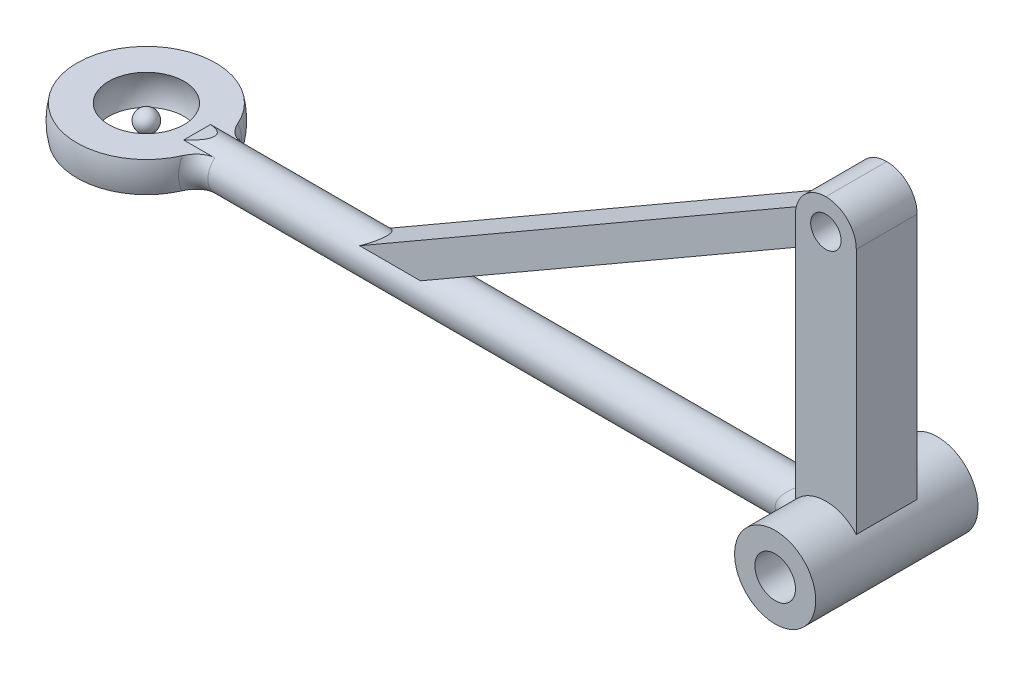
SolidWorks part; units mm, degrees
ref_plane "前视基准面" through (0, 0, 0) normal (0, 0, 1) x (1, 0, 0)
ref_plane "上视基准面" through (0, 0, 0) normal (0, 1, 0) x (1, 0, 0)
ref_plane "右视基准面" through (0, 0, 0) normal (1, 0, 0) x (0, 0, -1)
other "Configuration Table"
sketch "草图1" plane through (0, 0, 0) normal (0, 0, 1) x (1, 0, 0)
  line L0 (0, 0.75) -> (0, -0.75) construction
  line L1 (5, -0.75) -> (-5, -0.75)
  line L2 (5, -0.75) -> (5, 0.75)
  line L3 (5, 0.75) -> (-5, 0.75)
  line L4 (-5, -0.75) -> (-5, 0.75)
  line L5 (5, -0.75) -> (-5, 0.75) construction
  line L6 (5, 0.75) -> (-5, -0.75) construction
  circle A0 centre (0, 0) radius 3.5
  circle A1 centre (0, 0) radius 2
  dimension "D1" = 4
  dimension "D2" = 1.5
  dimension "D3" = 1.5
  dimension "D4" = 10
revolve "旋转1" add sketch "草图1" angle 360 about L0 region at (-2.7121, 0, 0)
sketch "草图2" plane through (0, 0, 0) normal (0, 0, 1) x (1, 0, 0)
  line L0 (0, 0) -> (35, 0) construction
  circle A0 centre (35, 0) radius 1
  circle A1 centre (35, 0) radius 2
  dimension "D2" = 2
  dimension "D3" = 1
  dimension "D1" = 35
extrude "凸台-拉伸1" add sketch "草图2" along normal mid plane 8 separate body
sketch "草图3" plane through (0, 0, 0) normal (0, 1, 0) x (1, 0, 0)
  line L0 (-0.5, 0) -> (0.5, 0)
  line L1 (37, 4) -> (33, 4) construction
  line L2 (35, 4) -> (35, 0) construction
  line L3 (35, 0) -> (0, 0) construction
  line L4 (2.5, 0) -> (33.9, 0)
  line L5 (2.5, 0) -> (2.5, 1)
  line L6 (2.5, 1) -> (33.9, 1)
  line L7 (33.9, 0) -> (33.9, 1)
  arc A0 (0.5, 0) -> (-0.5, 0) centre (0, 0) ccw
  dimension "D4" = 1
  dimension "D1" = 1
  dimension "D2" = 2.5
  dimension "D3" = 1.1
revolve "旋转2" add sketch "草图3" angle 360 about L4
sketch "草图4" plane through (0, 0, 0) normal (0, 0, 1) x (1, 0, 0)
  line L0 (2.5, 0.75) -> (2.5, 1)
  line L1 (2.5, 1) -> (3.3541, 1)
  line L2 (3.3541, 1) -> (2.5, 0.75)
  line L3 (3.3541, -0.75) -> (3.3541, 0.75) construction
  line L4 (0, 0) -> (3.8322, 0) construction
  line L5 (3.3541, -1) -> (2.5, -0.75)
  line L6 (2.5, -1) -> (3.3541, -1)
  line L7 (2.5, -0.75) -> (2.5, -1)
extrude "切除-拉伸1" cut sketch "草图4" against normal mid plane 10
fillet "圆角1" radius 1 3 edges at (33.0025, 0.1009, -0.9949) (3.3541, 0, -1) (3.3541, 0, 1)
sketch "草图5" plane through (0, 0, 0) normal (0, 0, 1) x (1, 0, 0)
  line L0 (35, 1.3229) -> (35, 0) construction
  line L1 (36.5, 1.3229) -> (33.5, 1.3229)
  line L2 (36.5, 1.3229) -> (36.5, 15)
  line L3 (36.5, 15) -> (33.5, 15)
  line L4 (33.5, 1.3229) -> (33.5, 15)
  line L5 (35, 15) -> (35, 13.5) construction
  circle A0 centre (35, 0) radius 2 construction
  circle A1 centre (35, 13.5) radius 0.75
  dimension "D3" = 1.5
  dimension "D4" = 1.5
  dimension "D1" = 3
  dimension "D2" = 15
extrude "凸台-拉伸2" add sketch "草图5" along normal mid plane 3
fillet "圆角2" radius 1.5 2 edges at (33.5, 15, 0) (36.5, 15, 0)
sketch "草图6" plane through (0, 0, 0) normal (0, 0, 1) x (1, 0, 0)
  line L0 (33.5, 13.5) -> (10.1173, 0)
  line L1 (33.5, 13.5) -> (33.5, 1.3229) construction
  line L2 (10.1173, 0) -> (13.1173, 0)
  line L3 (13.1173, 0) -> (33.5, 11.7679)
  line L4 (33.5, 11.7679) -> (33.5, 13.5)
  line L5 (13.1173, 0) -> (35, 0) construction
  arc A0 (35, 15) -> (33.5, 13.5) centre (35, 13.5) ccw construction
  dimension "D1" = 1.5
  dimension "D2" = 60
extrude "凸台-拉伸3" add sketch "草图6" along normal mid plane 1.5
